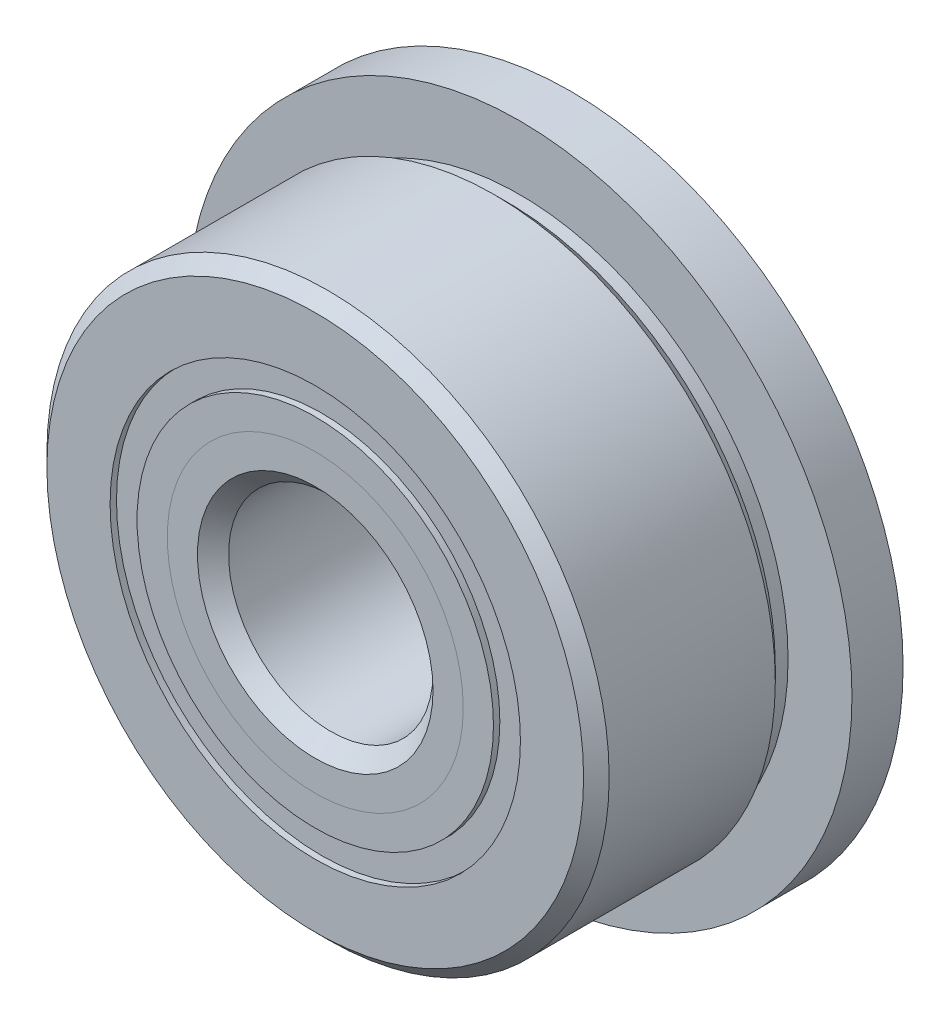
SolidWorks part; units mm, degrees
ref_plane "Front Plane" through (0, 0, 0) normal (0, 0, 1) x (1, 0, 0)
ref_plane "Top Plane" through (0, 0, 0) normal (0, 1, 0) x (1, 0, 0)
ref_plane "Right Plane" through (0, 0, 0) normal (1, 0, 0) x (0, 0, -1)
sketch "Sketch1" plane through (0, 0, 0) normal (1, 0, 0) x (0, 0, -1)
  line L0 (-3.9688, 0) -> (3.9688, 0) construction
  line L1 (0, 8.7312) -> (0, -8.7312) construction
  line L2 (3.5719, 8.7313) -> (-3.5719, 8.7312)
  line L3 (-3.5719, 8.7312) -> (-3.9688, 8.3344)
  line L4 (-3.9688, 8.3344) -> (-3.9688, 6.3718)
  line L5 (-3.9688, 6.3718) -> (-1.7639, 6.3718)
  line L6 (3.9688, 6.3718) -> (1.7639, 6.3718)
  line L7 (3.9688, 8.3344) -> (3.9688, 6.3718)
  line L8 (3.5719, 8.7313) -> (3.9688, 8.3344)
  line L9 (0, 8.7312) -> (0, 5.9531) construction
  line L10 (0, 5.9531) -> (0, 3.175) construction
  line L11 (3.9688, 0) -> (5.5563, 0) construction
  arc A0 (-1.7639, 6.3718) -> (1.7639, 6.3718) centre (0, 5.9531) cw
  point P14 (0, 3.175)
  dimension "D3" = 3.5278
  dimension "D1" = 45
  dimension "Width" = 7.9375
  dimension "OD" = 17.4625
  dimension "D2" = 0.3969
  dimension "Shaft Dia" = 6.35
  dimension "D4" = 0.4187
  dimension "Total Wd" = 9.525
revolve "Revolve1" add sketch "Sketch1" angle 360 about L0
sketch "Sketch2" plane through (0, 0, 0) normal (1, 0, 0) x (0, 0, -1)
  line L0 (-3.9688, 5.5344) -> (-1.7639, 5.5344)
  line L1 (-3.9688, 8.3344) -> (-3.9688, -8.3344) construction
  line L2 (-3.9688, 5.5344) -> (-3.9688, 4.596)
  line L3 (-3.9688, 4.596) -> (-3.0303, 3.6576)
  line L4 (-3.0303, 3.6576) -> (0, 3.6576)
  line L5 (0, 8.7312) -> (0, -8.7312) construction
  line L6 (0, 3.6576) -> (0, 4.1402)
  line L7 (0, 4.1402) -> (0, 3.175) construction
  line L8 (-3.9688, 5.5344) -> (-3.9688, 3.6576) construction
  line L9 (-3.9688, 3.6576) -> (-3.0303, 3.6576) construction
  arc A0 (-1.7639, 5.5344) -> (0, 4.1402) centre (0, 5.9531) ccw
  arc A1 (1.7639, 6.3718) -> (-1.7639, 6.3718) centre (0, 5.9531) ccw construction
  circle A2 centre (0, 5.9531) radius 1.8129 construction
  dimension "D1" = 45
revolve "Revolve2" add sketch "Sketch2" angle 360 about L0
sketch "Sketch3" plane through (0, 0, 0) normal (1, 0, 0) x (0, 0, -1)
  line L0 (-3.9688, 4.596) -> (-3.0303, 3.6576)
  line L1 (-3.0303, 3.6576) -> (0, 3.6576)
  line L2 (0, 3.6576) -> (0, 4.1402)
  line L3 (-3.9688, 4.596) -> (-3.9688, 3.6576)
  line L4 (-3.9688, 5.5344) -> (-3.9688, 3.6576) construction
  line L5 (-3.9688, 3.6576) -> (-3.4861, 3.175)
  line L6 (-3.4861, 3.175) -> (5.1594, 3.175)
  line L8 (5.1594, 3.175) -> (5.5563, 3.5719)
  line L10 (5.5563, 3.5719) -> (5.5563, 5.5344)
  line L11 (5.5563, 5.5344) -> (1.7639, 5.5344)
  line L13 (3.5719, 8.7313) -> (3.9688, 8.3344) construction
  circle A0 centre (0, 5.9531) radius 1.8129 construction
  arc A1 (1.7639, 5.5344) -> (0, 4.1402) centre (0, 5.9531) cw
revolve "Revolve3" add sketch "Sketch3" angle 360 about L0
sketch "Sketch5" plane through (0, 0, 0) normal (1, 0, 0) x (0, 0, -1)
  line L0 (3.9688, 8.3344) -> (3.9688, 6.3718) construction
  line L1 (3.9688, 7.3531) -> (2.3813, 7.3531)
  line L2 (3.9688, 7.3531) -> (3.9688, 10.3187)
  line L3 (3.9688, 10.3187) -> (2.3813, 10.3188)
  line L4 (2.3813, 7.3531) -> (2.3813, 10.3188)
  line L5 (5.5563, 0) -> (-3.9688, 0) construction
  dimension "D1" = 1.5875
  dimension "Flange OD" = 20.6375
revolve "Revolve5" add sketch "Sketch5" angle 360 about L5
sketch "Sketch6" plane through (0, 0, 0) normal (1, 0, 0) x (0, 0, -1)
  line L0 (1.5875, 8.7313) -> (1.9844, 8.3344)
  line L1 (3.5719, 8.7313) -> (-3.5719, 8.7313) construction
  line L2 (1.9844, 8.3344) -> (2.3813, 8.3344)
  line L3 (2.3813, 8.3344) -> (2.3813, 8.7313)
  line L4 (2.3813, 8.7313) -> (1.5875, 8.7313)
  line L5 (3.5719, 8.7313) -> (3.9688, 8.3344) construction
  line L6 (2.3813, 7.3531) -> (2.3813, 10.3188) construction
  dimension "D1" = 0.3969
revolve "Cut-Revolve1" cut sketch "Sketch6" angle 360 about L0
sketch "Sketch4" plane through (0, 0, 0) normal (1, 0, 0) x (0, 0, -1)
  line L0 (-1.8129, 5.9531) -> (1.8129, 5.9531)
  circle A1 centre (0, 5.9531) radius 1.8129 construction
  arc A2 (-1.8129, 5.9531) -> (1.8129, 5.9531) centre (0, 5.9531) cw
  arc A3 (1.7639, 6.3718) -> (-1.7639, 6.3718) centre (0, 5.9531) ccw construction
revolve "Revolve4" add sketch "Sketch4" angle 360 about L0
ref_axis "Axis1" through (0, 0, -3.9688) along (0, 0, 1)
pattern_circular "CirPattern1" count 10 every 36 about axis through (0, 0, -3.9688) along (0, 0, 1) of bodies 104
sketch "Sketch7" plane through (0, 0, 0) normal (1, 0, 0) x (0, 0, -1)
  line L0 (-3.9688, 6.3718) -> (-1.7639, 6.3718) construction
  line L1 (-3.7703, 6.3718) -> (-1.8129, 6.3718)
  line L2 (-3.7703, 6.3718) -> (-3.7703, 5.5344)
  line L3 (-3.7703, 5.5344) -> (-1.8129, 5.5344)
  line L4 (-1.8129, 6.3718) -> (-1.8129, 5.5344)
  line L5 (-3.9688, 5.5344) -> (-1.7639, 5.5344) construction
  line L6 (-3.5719, 8.7312) -> (-3.9688, 8.3344) construction
  line L7 (3.9688, 6.3718) -> (1.7639, 6.3718) construction
  line L8 (3.7703, 6.3718) -> (1.8129, 6.3718)
  line L9 (3.7703, 6.3718) -> (3.7703, 5.5344)
  line L10 (3.7703, 5.5344) -> (1.8129, 5.5344)
  line L11 (1.8129, 6.3718) -> (1.8129, 5.5344)
  line L12 (5.5563, 5.5344) -> (1.7639, 5.5344) construction
  line L13 (3.5719, 8.7313) -> (3.9688, 8.3344) construction
  circle A0 centre (0, 5.9531) radius 1.8129 construction
  point P10 (-3.7703, 8.5328)
  point P21 (3.7703, 8.5328)
revolve "Revolve6" add sketch "Sketch7" angle 360 about L0
equation "\"D2@Sketch1\" = \"Width@Sketch1\"*.05"
equation "\"D3@Sketch1\" = \"Width@Sketch1\"/2.25"
equation "\"D4@Sketch1\" = (((\"OD@Sketch1\"-\"Width@Sketch1\")/2)/3.25)/3.5"
equation "\"D2@CirPattern1\" = 360/\"Balls@CirPattern1\""
